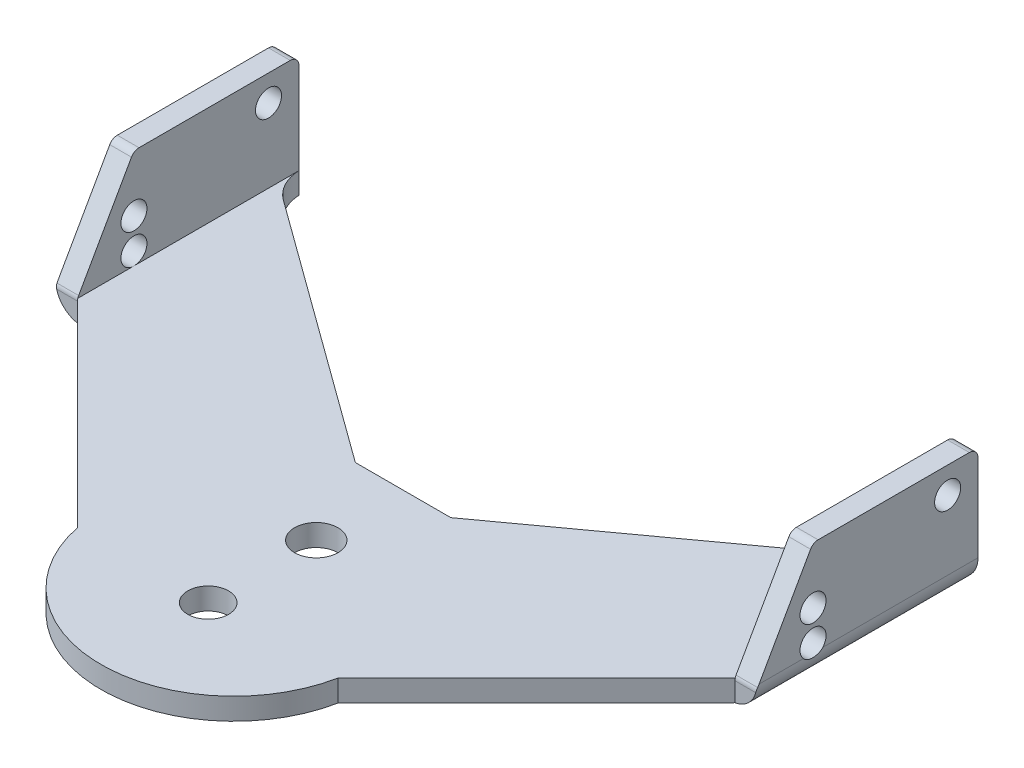
SolidWorks part; units mm, degrees
material "AISI 1020"
ref_plane "Front Plane" through (0, 0, 0) normal (0, 0, 1) x (1, 0, 0)
ref_plane "Top Plane" through (0, 0, 0) normal (0, 1, 0) x (1, 0, 0)
ref_plane "Right Plane" through (0, 0, 0) normal (1, 0, 0) x (0, 0, -1)
sketch "Sketch1" plane through (0, 0, 0) normal (0, 1, 0) x (1, 0, 0)
  line L0 (-15, -22.5) -> (15, -22.5) construction
  line L1 (-5.5, 0) -> (5.5, 0)
  line L2 (5.5, 0) -> (37.8607, 23.5114)
  line L3 (5.5, 0) -> (3.4438, 0) construction
  line L4 (15, -22.5) -> (37.8607, 0.3607)
  line L5 (15, -22.5) -> (30.1904, -22.5) construction
  line L6 (0, 0) -> (0, -34.8) construction
  line L7 (37.8607, 23.5114) -> (37.8607, 0.3607)
  line L8 (-37.8607, 23.5114) -> (-37.8607, 0.3607)
  line L9 (-15, -22.5) -> (-37.8607, 0.3607)
  line L10 (-5.5, 0) -> (-37.8607, 23.5114)
  arc A0 (-15, -22.5) -> (15, -22.5) centre (0, -19.5037) ccw
  circle A1 centre (0, -22.45) radius 2.35
  circle A2 centre (0, -10) radius 2.5
  point P6 (0, 0)
  point P11 (0, -22.5)
  point P13 (0, -34.8)
  dimension "D8" = 4.7
  dimension "D9" = 5
  dimension "D1" = 11
  dimension "D2" = 40
  dimension "D3" = 36
  dimension "D4" = 45
  dimension "D5" = 34.8
  dimension "D6" = 30
  dimension "D7" = 22.5
  dimension "D10" = 12.35
  dimension "D11" = 10
extrude "Boss-Extrude1" add sketch "Sketch1" along normal blind 2.5 contours L9 A0 L4 L7 L2 L1 L10 L8 region at (0, 0, 5.7228)
sketch "Sketch2" plane through (37.8607, 0, 0) normal (1, 0, 0) x (0, 0, -1)
  line L0 (0.3607, 0) -> (25.8607, 0)
  line L1 (25.8607, 0) -> (25.8607, 14)
  line L2 (25.8607, 14) -> (6.8607, 14)
  line L4 (0.3607, 0) -> (0.3607, 2.5)
  line L5 (0.3607, 2.5) -> (6.8607, 14)
  circle A0 centre (6.8607, 7.5) radius 1.5
  circle A1 centre (22.3607, 11) radius 1.5
  circle A2 centre (6.8607, 4) radius 1.5
  point P14 (0, 0)
  dimension "D4" = 3
  dimension "D1" = 14
  dimension "D2" = 19
  dimension "D3" = 25.5
  dimension "D5" = 6.5
  dimension "D6" = 3.5
  dimension "D7" = 3
  dimension "D8" = 3.5
extrude "Boss-Extrude2" add sketch "Sketch2" along normal blind 2.5
mirror "Mirror1" about plane through (0, 0, 0) normal (1, 0, 0) of "Boss-Extrude2"
fillet "Fillet1" radius 5 2 edges at (37.8607, 1.25, -23.5114) (-37.8607, 1.25, -23.5114)
fillet "Fillet2" radius 1 6 edges at (-39.1107, 2.5, -0.3607) (39.1107, 2.5, -0.3607) (-39.1107, 14, -25.8607) (-39.1107, 14, -6.8607) (39.1107, 14, -25.8607) (39.1107, 14, -6.8607)
fillet "Fillet3" radius 3 2 edges at (-40.3607, 0, -13.1107) (40.3607, 0, -13.1107)
